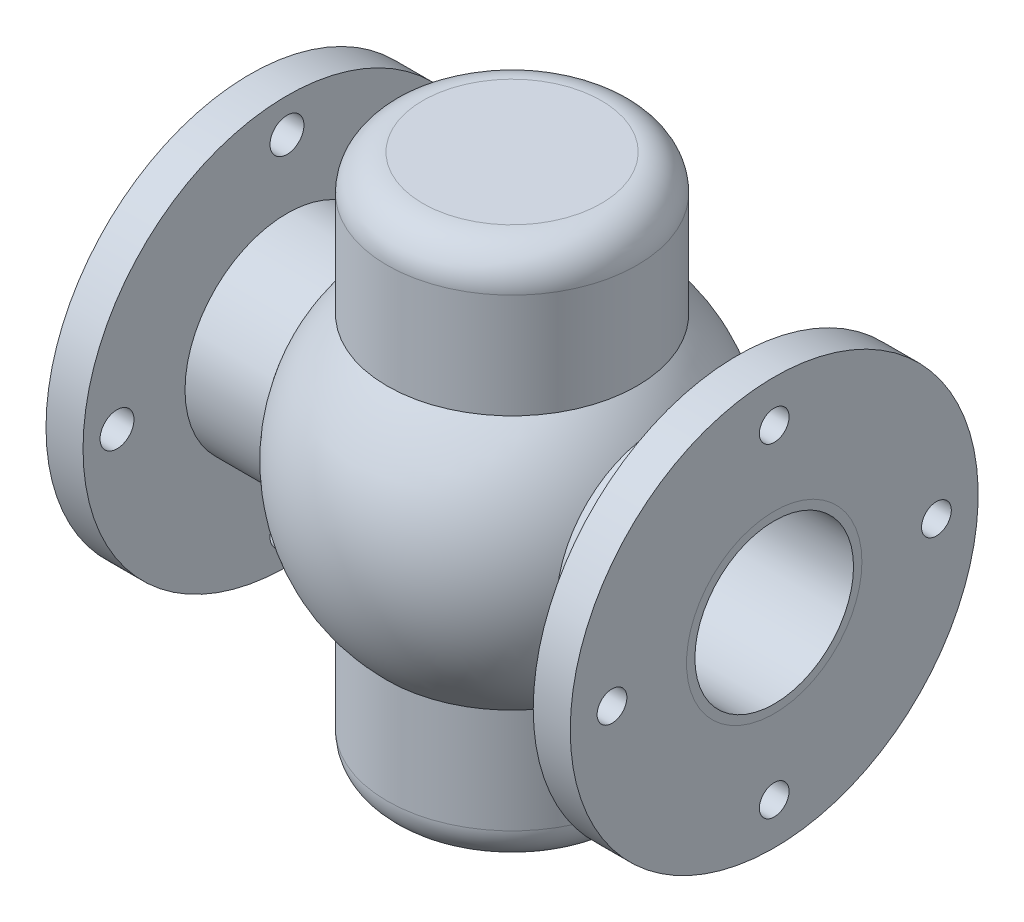
SolidWorks part; units mm, degrees
material "Cast Stainless Steel"
ref_plane "Front" through (0, 0, 0) normal (0, 0, 1) x (1, 0, 0)
ref_plane "Top" through (0, 0, 0) normal (0, 1, 0) x (1, 0, 0)
ref_plane "Right" through (0, 0, 0) normal (1, 0, 0) x (0, 0, -1)
other "Configuration Table"
sketch "Sketch1" plane through (0, 0, 0) normal (1, 0, 0) x (0, 0, -1)
  circle A0 centre (0, 0) radius 57.15
  dimension "D1" = 114.3
extrude "Base-Extrude" add sketch "Sketch1" along normal mid plane 300
sketch "Sketch2" plane through (0, 0, 0) normal (0, 1, 0) x (1, 0, 0)
  circle A0 centre (0, 0) radius 70
  dimension "D1" = 140
extrude "Boss-Extrude1" add sketch "Sketch2" along normal blind 150 and the other way blind 150
sketch "Sketch3" plane through (0, 0, 0) normal (0, 0, 1) x (1, 0, 0)
  line L0 (0, -115.863) -> (0, 215.6893) construction
  line L1 (0, 150) -> (0, -150) construction
  line L2 (0, -100) -> (0, 100)
  arc A0 (0, 100) -> (0, -100) centre (0, 0) cw
  dimension "D1" = 100
revolve "Boss-Revolve1" add sketch "Sketch3" angle 360 about L0
fillet "Fillet1" radius 20 2 edges at (0, -150, 70) (0, 150, 70)
shell "Shell1" [suppressed] thickness 10.5
sketch "Sketch18" plane through (-150, 0, 0) normal (-1, 0, 0) x (0, 0, 1)
  circle A0 centre (0, 0) radius 44.45
  dimension "D1" = 88.9
extrude "Cut-Extrude3" cut sketch "Sketch18" against normal through all
sketch "Sketch5" [suppressed] plane through (0, 0, 0) normal (0, 0, 1) x (1, 0, 0)
  line L0 (190, 198.3801) -> (180, 198.3801)
  line L1 (180, 198.3801) -> (180, 210)
  line L2 (180, 210) -> (185, 210)
  line L3 (180, 210) -> (-180, 210) construction
  line L4 (180, 160) -> (180, 210) construction
  line L5 (0, 0) -> (0, 105.4969) construction
  line L6 (0, 120) -> (0, 71.4143) construction
  arc A0 (190, 198.3801) -> (185, 210) centre (173.9977, 198.3801) ccw
  dimension "D1" = 16.0023
  dimension "D2" = 10
  dimension "D3" = 5
revolve "Boss-Revolve3" [suppressed] add sketch "Sketch5" angle 360 about L5
sketch "Sketch6" plane through (0, 150, 0) normal (0, 1, 0) x (-1, 0, 0)
  circle A0 centre (0, 0) radius 60
  dimension "D1" = 120
extrude "Boss-Extrude2" [suppressed] add sketch "Sketch6" along normal blind 30
sketch "Sketch7" [suppressed] plane through (0, 180, 0) normal (0, 1, 0) x (-1, 0, 0)
  circle A0 centre (0, 0) radius 50
  dimension "D1" = 100
extrude "Boss-Extrude3" [suppressed] add sketch "Sketch7" along normal blind 25
sketch "Sketch8" [suppressed] plane through (0, 205, 0) normal (0, 1, 0) x (-1, 0, 0)
  circle A0 centre (0, 0) radius 35
  dimension "D1" = 70
extrude "Boss-Extrude4" [suppressed] add sketch "Sketch8" along normal blind 10
sketch "Sketch9" [suppressed] plane through (0, 215, 0) normal (0, 1, 0) x (-1, 0, 0)
  circle A0 centre (0, 0) radius 12.5
  dimension "D1" = 25
extrude "Boss-Extrude5" [suppressed] add sketch "Sketch9" along normal blind 35
sketch "hexagon2" [suppressed] plane through (-2.3581, 250, -8.0849) normal (0, 1, 0) x (-1, 0, 0)
  line L0 (17.6378, 8.4916) -> (7.2876, 25.6052)
  line L1 (7.2876, 25.6052) -> (-12.7082, 25.1985)
  line L2 (-12.7082, 25.1985) -> (-22.354, 7.6782)
  line L3 (-22.354, 7.6782) -> (-12.0038, -9.4354)
  line L4 (-12.0038, -9.4354) -> (7.9921, -9.0287)
  line L5 (7.9921, -9.0287) -> (17.6378, 8.4916)
  circle A0 centre (-2.3581, 8.0849) radius 20 construction
  dimension "Outside Diameter" = 40
extrude "Boss-Extrude6" [suppressed] add sketch "hexagon2" against normal blind 15
sketch "Sketch13" plane through (0, 0, 0) normal (0, 0, 1) x (1, 0, 0)
  line L0 (0, 0) -> (246.3426, 0) construction
  line L1 (150, 0) -> (82.0602, 0) construction
  line L2 (126.15, 57.15) -> (126.15, 114.3)
  line L3 (126.15, 114.3) -> (146.9, 114.3)
  line L4 (146.9, 114.3) -> (146.9, 67.5)
  line L5 (146.9, 67.5) -> (150, 67.5)
  line L6 (150, 67.5) -> (150, 57.15)
  line L7 (150, 57.15) -> (126.15, 57.15)
  line L8 (150, 57.15) -> (82.0602, 57.15) construction
  line L9 (150, -57.15) -> (150, 57.15) construction
  dimension "D1" = 114.3
  dimension "D2" = 67.5
  dimension "D3" = 20.75
  dimension "D4" = 3.1
revolve "Boss-Revolve4" add sketch "Sketch13" angle 360 about L0
mirror "Mirror2" about plane through (0, 0, 0) normal (1, 0, 0) of "Boss-Revolve4"
sketch "Sketch14" plane through (146.9, 0, 0) normal (1, 0, 0) x (0, 0, -1)
  line L1 (0, 0) -> (0, 114.3) construction
  line L2 (0, 0) -> (0, 95.25) construction
  circle A0 centre (0, 95.25) radius 9.5
  circle A1 centre (0, 0) radius 114.3 construction
  dimension "D1" = 19
  dimension "D2" = 95.25
  dimension "D3" = 0
extrude "Cut-Extrude1" [suppressed] cut sketch "Sketch14" against normal up to next
pattern_circular "CirPattern1" [suppressed] count 4 over 360 about axis through (0, 0, 0) along (1, 0, 0)
sketch "Sketch15" plane through (-146.9, 0, 0) normal (-1, 0, 0) x (0, 0, 1)
  line L0 (0, 0) -> (0, 62.7443) construction
  line L1 (0, 0) -> (0, 95.25) construction
  circle A1 centre (0, 95.25) radius 9.5
  circle A2 centre (0, 0) radius 95.25 construction
  dimension "D1" = 19
  dimension "D2" = 190.5
  dimension "D3" = 0
extrude "Cut-Extrude2" cut sketch "Sketch15" against normal up to next
pattern_circular "CirPattern2" count 4 over 360 about axis through (0, 0, 0) along (1, 0, 0) of "Cut-Extrude2"
sketch "Sketch22" plane through (146.9, 0, 0) normal (1, 0, 0) x (0, 0, -1)
  circle A0 centre (0, 0) radius 67.5 construction
  circle A1 centre (0, 0) radius 67.5
extrude "Cut-Extrude5" cut sketch "Sketch22" along normal up to surface (3.1 mm away) up to face at (150, 0, 44.45)
sketch "Sketch24" plane through (146.9, 0, 0) normal (1, 0, 0) x (0, 0, -1)
  circle A0 centre (0, 0) radius 49.15
split line "Split Line1"
hole_wizard "5/8 Clearance Hole1" positions "Sketch25" profile "Sketch26" hole size "5/8" standard "Ansi Inch" end condition through all
sketch "Sketch25" plane through (126.15, -86.9453, 61.2299) normal (-1, 0, 0) x (0, 0, 1)
  line L0 (-61.2299, 86.9453) -> (160.2598, 86.9453) construction
  line L1 (-61.2299, 86.9453) -> (-61.2299, 296.6144) construction
  line L2 (-61.2299, 86.9453) -> (-291.9631, 86.9453) construction
  line L3 (-61.2299, 86.9453) -> (-61.2299, -121.1078) construction
  circle A0 centre (-61.2299, 86.9453) radius 90.9114 construction
  point P0 (-61.2299, 177.798)
  point P1 (29.6815, 86.9453)
  point P2 (-61.2299, -3.9661)
  point P3 (-152.1413, 86.9453)
sketch "Sketch26" plane through (126.15, 90.8528, 0) normal (0, 1, 0) x (0, 0, 1)
  line L0 (0, 0) -> (0, 20.75)
  line L1 (0, 20.75) -> (8.3337, 20.75)
  line L2 (8.3337, 20.75) -> (8.3337, 0)
  line L5 (8.3337, 0) -> (0, 0)
  line L11 (0, -6.35) -> (0, 107.95) construction
  dimension "Thru Hole Dia." = 16.6675
  dimension "Thru Hole Depth" = 20.75
